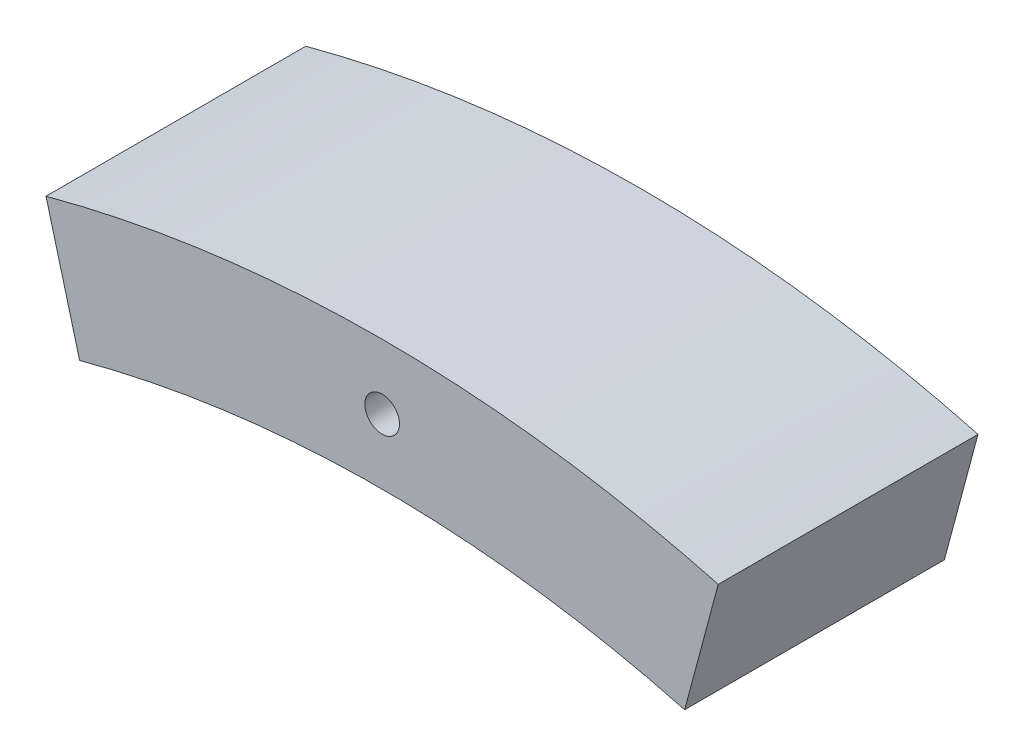
SolidWorks part; units mm, degrees
ref_plane "Front Plane" through (0, 0, 0) normal (0, 0, 1) x (1, 0, 0)
ref_plane "Top Plane" through (0, 0, 0) normal (0, 1, 0) x (1, 0, 0)
ref_plane "Right Plane" through (0, 0, 0) normal (1, 0, 0) x (0, 0, -1)
sketch "Sketch1" plane through (0, 0, 0) normal (0, 0, 1) x (1, 0, 0)
  line L0 (0, 0) -> (0, 150) construction
  line L1 (0, 0) -> (38.8229, 144.8889) construction
  line L2 (0, 0) -> (-38.8229, 144.8889) construction
  line L3 (0, 0) -> (129.9038, 75) construction
  line L4 (0, 0) -> (106.066, 106.066) construction
  line L5 (0, 0) -> (75, 129.9038) construction
  line L6 (0, 0) -> (144.8889, -38.8229) construction
  line L7 (0, 0) -> (150, 0) construction
  line L8 (0, 0) -> (144.8889, 38.8229) construction
  line L9 (0, 0) -> (75, -129.9038) construction
  line L10 (0, 0) -> (106.066, -106.066) construction
  line L11 (0, 0) -> (129.9038, -75) construction
  line L12 (0, 0) -> (-38.8229, -144.8889) construction
  line L13 (0, 0) -> (0, -150) construction
  line L14 (0, 0) -> (38.8229, -144.8889) construction
  line L15 (0, 0) -> (-129.9038, -75) construction
  line L16 (0, 0) -> (-106.066, -106.066) construction
  line L17 (0, 0) -> (-75, -129.9038) construction
  line L18 (0, 0) -> (-144.8889, 38.8229) construction
  line L19 (0, 0) -> (-150, 0) construction
  line L20 (0, 0) -> (-144.8889, -38.8229) construction
  line L21 (0, 0) -> (-75, 129.9038) construction
  line L22 (0, 0) -> (-106.066, 106.066) construction
  line L23 (0, 0) -> (-129.9038, 75) construction
  line L24 (-34.9406, 130.4) -> (-38.8229, 144.8889)
  line L25 (34.9406, 130.4) -> (38.8229, 144.8889)
  circle A0 centre (0, 0) radius 107.5 construction
  circle A1 centre (0, 0) radius 150 construction
  arc A2 (-34.9406, 130.4) -> (34.9406, 130.4) centre (0, 0) cw
  arc A3 (-38.8229, 144.8889) -> (38.8229, 144.8889) centre (0, 0) cw
  circle A4 centre (0, 142.5) radius 2
  point P30 (0, 0)
  dimension "D1" = 215
  dimension "D2" = 300
  dimension "D6" = 135
  dimension "D8" = 4
  dimension "D3" = 15
  dimension "D4" = 15
  dimension "D7" = 142.5
  dimension "D5" = 8
extrude "Boss-Extrude1" add sketch "Sketch1" along normal blind 15 and the other way blind 15
